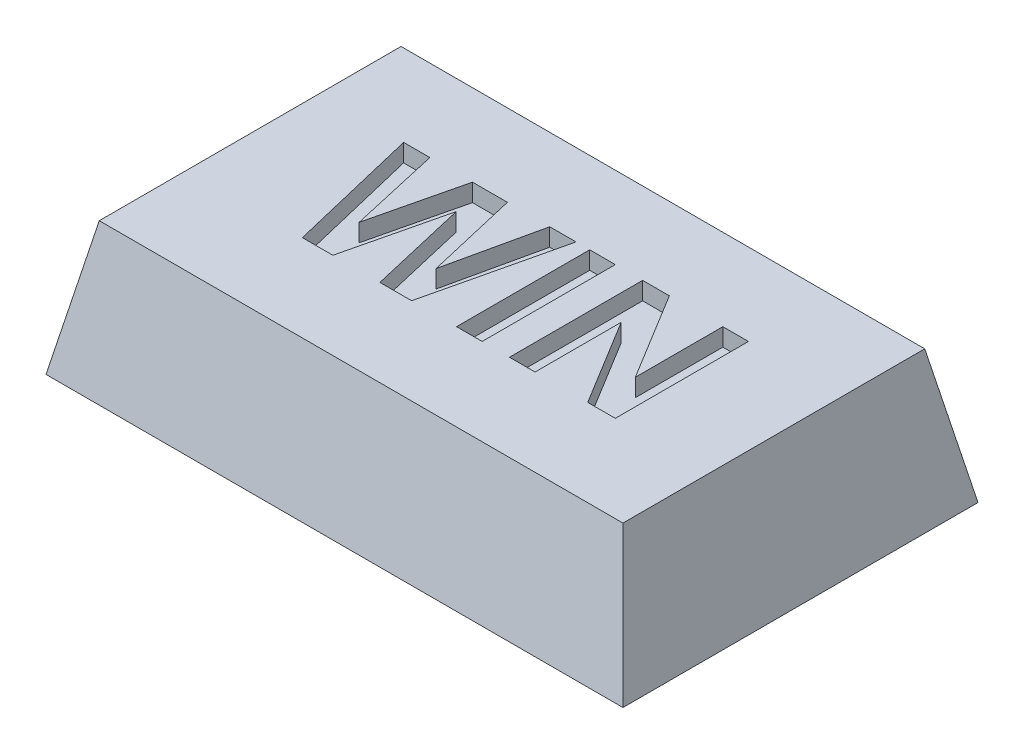
SolidWorks part; units mm, degrees
ref_plane "Front Plane" through (0, 0, 0) normal (0, 0, 1) x (1, 0, 0)
ref_plane "Top Plane" through (0, 0, 0) normal (0, 1, 0) x (1, 0, 0)
ref_plane "Right Plane" through (0, 0, 0) normal (1, 0, 0) x (0, 0, -1)
sketch "Sketch1" plane through (0, 0, 0) normal (0, 1, 0) x (1, 0, 0)
  line L1 (0, 0) -> (13, 0)
  line L2 (0, 0) -> (0, 8)
  line L3 (0, 8) -> (13, 8)
  line L4 (13, 0) -> (13, 8)
  dimension "D1" = 8
  dimension "D2" = 13
extrude "Boss-Extrude1" add sketch "Sketch1" along normal blind 3
sketch "Sketch2" plane through (0, 0, 0) normal (0, 0, 1) x (1, 0, 0)
  line L0 (0, 0) -> (0.6, 3)
  line L1 (0, 3) -> (13, 3) construction
  line L2 (0.6, 3) -> (0, 3)
  line L3 (0, 3) -> (0, 0)
  line L4 (13, 0) -> (12.4, 3)
  line L5 (12.4, 3) -> (13, 3)
  line L6 (13, 3) -> (13, 0)
  dimension "D1" = 0.6
  dimension "D2" = 0.6
extrude "Cut-Extrude1" cut sketch "Sketch2" against normal through all both and the other way through all
sketch "Sketch3" plane through (0, 0, 0) normal (1, 0, 0) x (0, 0, -1)
  line L0 (0, 0) -> (0.6, 3)
  line L1 (8, 3) -> (0, 3) construction
  line L2 (0.6, 3) -> (0, 3)
  line L3 (0, 3) -> (0, 0)
  line L4 (8, 3) -> (7.4, 3)
  line L5 (7.4, 3) -> (8, 0)
  line L6 (8, 3) -> (8, 0)
  dimension "D1" = 0.6
  dimension "D2" = 0.6
extrude "Cut-Extrude2" cut sketch "Sketch3" along normal through all both and the other way through all
sketch "Sketch4" plane through (0, 0, 0) normal (0, -1, 0) x (1, 0, 0)
  line L1 (6.5, 0) -> (6.5, -8) construction
  line L2 (13, -8) -> (0, -8) construction
  line L3 (0, 0) -> (13, 0) construction
  circle A0 centre (6.5, -3.75) radius 1.8
  dimension "D1" = 3.6
  dimension "D2" = 0
  dimension "D3" = 3.75
extrude "Cut-Extrude3" cut sketch "Sketch4" against normal blind 0.8
sketch "Sketch5" plane through (0, 0, 0) normal (0, -1, 0) x (1, 0, 0)
  line L5 (0, 0) -> (13, 0) construction
  line L6 (2.5, -8) -> (10.5, -8)
  line L7 (2.5, -8) -> (2.5, -7)
  line L8 (2.5, -7) -> (10.5, -7)
  line L9 (10.5, -8) -> (10.5, -7)
  point P2 (6.5, 0)
  dimension "D1" = 1
  dimension "D2" = 4
  dimension "D3" = 4
extrude "Boss-Extrude2" add sketch "Sketch5" along normal blind 2
fillet "Fillet1" radius 4 2 edges at (10.5, -2, -7.5) (2.5, -2, -7.5)
sketch "Sketch6" plane through (0, 3, 0) normal (0, 1, 0) x (1, 0, 0)
  text T0 "WIN" font "Arial" height 3
extrude "Cut-Extrude4" cut sketch "Sketch6" against normal blind 0.4
